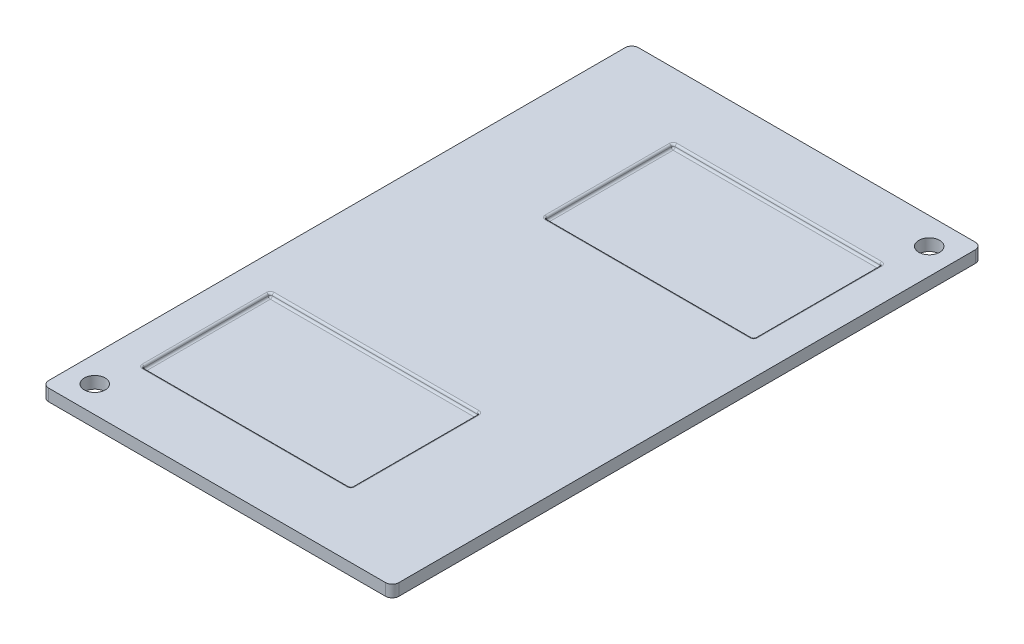
SolidWorks part; units mm, degrees
ref_plane "Front Plane" through (0, 0, 0) normal (0, 0, 1) x (1, 0, 0)
ref_plane "Top Plane" through (0, 0, 0) normal (0, 1, 0) x (1, 0, 0)
ref_plane "Right Plane" through (0, 0, 0) normal (1, 0, 0) x (0, 0, -1)
sketch "Sketch1" plane through (0, 0, 0) normal (0, 1, 0) x (1, 0, 0)
  line L1 (-35.8775, -62.8269) -> (35.8775, -62.8269)
  line L2 (-37.2999, -61.4045) -> (-37.2999, 61.4045)
  line L3 (-35.8775, 62.8269) -> (35.8775, 62.8269)
  line L4 (37.2999, -61.4045) -> (37.2999, 61.4045)
  line L5 (-37.2999, -62.8269) -> (37.2999, 62.8269) construction
  line L6 (-37.2999, 62.8269) -> (37.2999, -62.8269) construction
  arc A0 (-37.2999, 61.4045) -> (-35.8775, 62.8269) centre (-35.8775, 61.4045) cw
  arc A1 (35.8775, 62.8269) -> (37.2999, 61.4045) centre (35.8775, 61.4045) cw
  arc A2 (35.8775, -62.8269) -> (37.2999, -61.4045) centre (35.8775, -61.4045) ccw
  arc A3 (-35.8775, -62.8269) -> (-37.2999, -61.4045) centre (-35.8775, -61.4045) cw
  point P0 (0, 0)
  dimension "D3" = 1.4224
  dimension "D1" = 74.5998
  dimension "D2" = 125.6538
extrude "Extrude1" add sketch "Sketch1" along normal blind 2.54
sketch "Sketch2" plane through (0, 2.54, 0) normal (0, 1, 0) x (1, 0, 0)
  line L0 (-37.2999, 61.4045) -> (-37.2999, -61.4045) construction
  line L1 (-14.5161, 48.8569) -> (29.9339, 48.8569)
  line L2 (-14.5161, 48.8569) -> (-14.5161, 21.5519)
  line L3 (-14.5161, 21.5519) -> (29.9339, 21.5519)
  line L4 (29.9339, 48.8569) -> (29.9339, 21.5519)
  line L5 (-29.9339, -21.5519) -> (14.5161, -21.5519)
  line L6 (-29.9339, -21.5519) -> (-29.9339, -48.8569)
  line L7 (-29.9339, -48.8569) -> (14.5161, -48.8569)
  line L8 (14.5161, -21.5519) -> (14.5161, -48.8569)
  line L9 (37.2999, -61.4045) -> (37.2999, 61.4045) construction
  line L11 (35.8775, 62.8269) -> (-35.8775, 62.8269) construction
  line L12 (-35.8775, -62.8269) -> (35.8775, -62.8269) construction
  dimension "D1" = 44.45
  dimension "D2" = 44.45
  dimension "D3" = 27.305
  dimension "D4" = 27.305
  dimension "D5" = 7.366
  dimension "D6" = 7.366
  dimension "D7" = 13.97
  dimension "D8" = 13.97
extrude "Extrude2" cut sketch "Sketch2" against normal blind 0.8382
fillet "Fillet1" radius 0.4191 16 edges at (7.7089, 1.7018, -48.8569) (29.9339, 1.7018, -35.2044) (7.7089, 1.7018, -21.5519) (-14.5161, 1.7018, -35.2044) (-7.7089, 1.7018, 21.5519) (14.5161, 1.7018, 35.2044) (-7.7089, 1.7018, 48.8569) (-29.9339, 1.7018, 35.2044) (7.7089, 2.54, -48.8569) (29.9339, 2.54, -35.2044) (-14.5161, 2.54, -35.2044) (7.7089, 2.54, -21.5519) (14.5161, 2.54, 35.2044) (-7.7089, 2.54, 48.8569) (-29.9339, 2.54, 35.2044) (-7.7089, 2.54, 21.5519)
sketch "Sketch3" plane through (0, 2.54, 0) normal (0, 1, 0) x (1, 0, 0)
  circle A1 centre (31.75, 57.15) radius 2.2225 construction
  circle A2 centre (-31.75, -57.15) radius 2.2225 construction
  circle A3 centre (31.75, 57.15) radius 2.2225
  circle A4 centre (-31.75, -57.15) radius 2.2225
extrude "Cut-Extrude1" cut sketch "Sketch3" against normal through all
